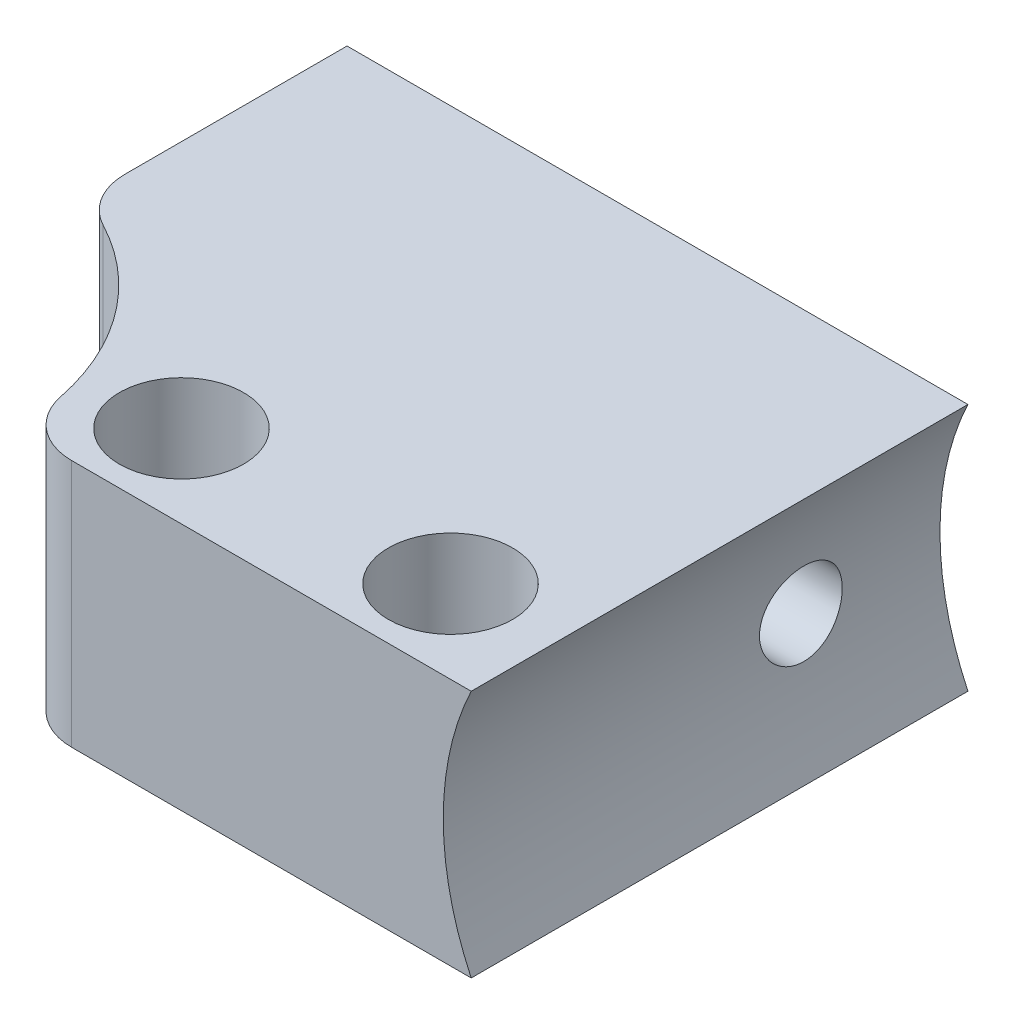
SolidWorks part; units mm, degrees
ref_plane "前视基准面" through (0, 0, 0) normal (0, 0, 1) x (1, 0, 0)
ref_plane "上视基准面" through (0, 0, 0) normal (0, 1, 0) x (1, 0, 0)
ref_plane "右视基准面" through (0, 0, 0) normal (1, 0, 0) x (0, 0, -1)
other "Configuration Table"
sketch "草图1" plane through (0, 0, 0) normal (0, 1, 0) x (1, 0, 0)
  line L1 (0, 0) -> (30, 0)
  line L2 (0, 0) -> (0, -10.7335)
  line L3 (10.6969, -24) -> (30, -24)
  line L4 (30, 0) -> (30, -24)
  arc A0 (7.7576, -21.6) -> (1.6, -13.3868) centre (-4, -24) ccw
  arc A1 (7.7576, -21.6) -> (10.6969, -24) centre (10.6969, -21) ccw
  arc A2 (1.6, -13.3868) -> (0, -10.7335) centre (3, -10.7335) cw
  circle A3 centre (12, -20) radius 3
  circle A4 centre (25, -20) radius 3
  dimension "D3" = 24
  dimension "D2" = 3
  dimension "D4" = 6
  dimension "D5" = 6
  dimension "D1" = 30
  dimension "D6" = 13
  dimension "D7" = 5
  dimension "D8" = 4
  dimension "D9" = 4
extrude "凸台-拉伸1" add sketch "草图1" along normal blind 12
sketch "草图2" plane through (0, 0, 0) normal (0, 0, -1) x (-1, 0, 0)
  line L0 (-30, 12) -> (-30, 0) construction
  line L1 (-30, 12) -> (-30, 0)
  arc A0 (-30, 0) -> (-30, 12) centre (-42.6491, 6) ccw
  point P5 (-30, 6)
  dimension "D1" = 28
extrude "切除-拉伸1" cut sketch "草图2" against normal through all
sketch "草图3" plane through (0, 0, 0) normal (-1, 0, 0) x (0, 0, 1)
  line L0 (0, 6) -> (24, 6) construction
  line L1 (0, 12) -> (0, 0) construction
  line L2 (24, 12) -> (24, 0) construction
  line L3 (0, 2.75) -> (0, 9.25)
  line L4 (0, 9.25) -> (4.2535, 10)
  line L5 (4.2535, 10) -> (4.2535, 2)
  line L6 (0, 2.75) -> (4.2535, 2)
  point P10 (4.2535, 6)
  dimension "D1" = 6.5
  dimension "D2" = 8
  dimension "D3" = 80
extrude "切除-拉伸2" cut sketch "草图3" against normal blind 23
sketch "草图4" plane through (0, 0, 0) normal (-1, 0, 0) x (0, 0, 1)
  line L0 (4.2535, 10) -> (4.2535, 2)
  arc A0 (4.2535, 10) -> (4.2535, 2) centre (6.7213, 6) cw
  circle A1 centre (6.7213, 6) radius 2
  dimension "D1" = 4.7
  dimension "D2" = 4
extrude "切除-拉伸3" cut sketch "草图4" against normal blind 3
extrude "切除-拉伸4" cut sketch "草图4<2>" against normal through all contours A1
sketch "草图4<2>" plane through (0, 0, 0) normal (-1, 0, 0) x (0, 0, 1) same geometry as "草图4"
